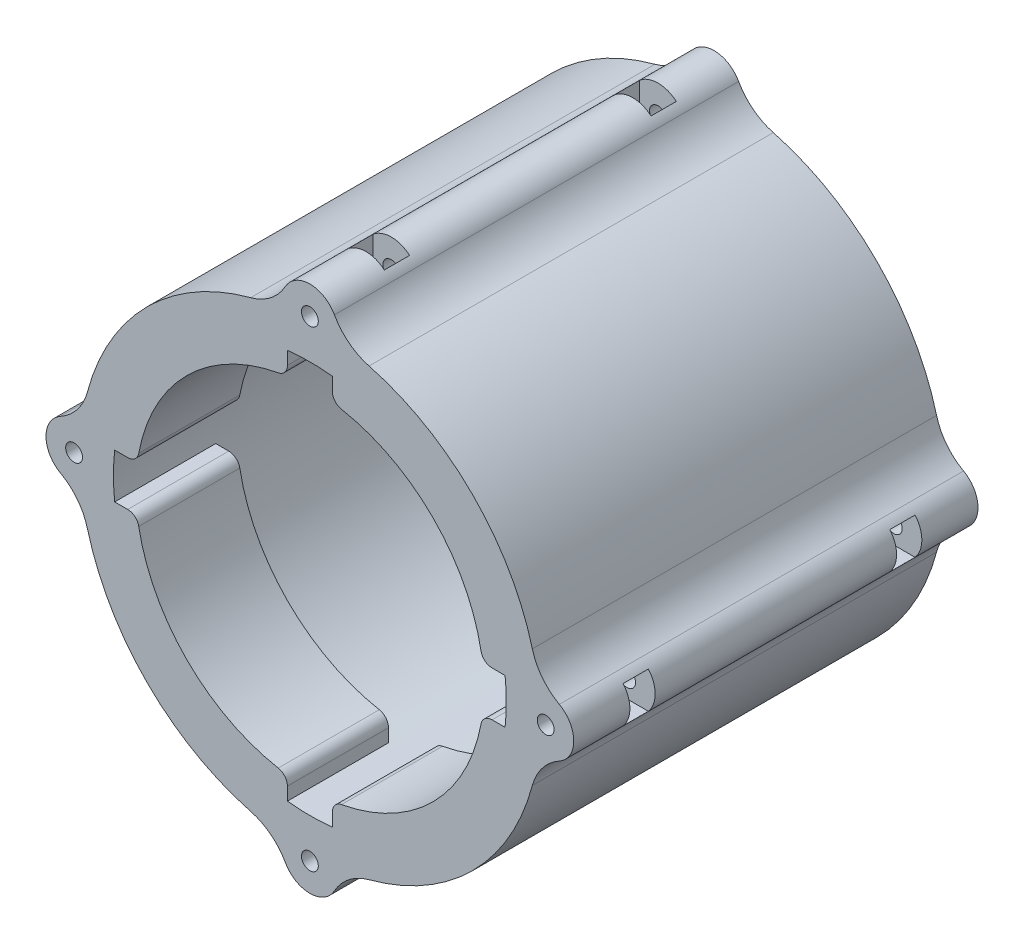
SolidWorks part; units mm, degrees
ref_plane "Ön Düzlem" through (0, 0, 0) normal (0, 0, 1) x (1, 0, 0)
ref_plane "Üst Düzlem" through (0, 0, 0) normal (0, 1, 0) x (1, 0, 0)
ref_plane "Sağ Düzlem" through (0, 0, 0) normal (1, 0, 0) x (0, 0, -1)
sketch "Çizim1" plane through (0, 0, 0) normal (0, 0, 1) x (1, 0, 0)
  circle A0 centre (0, 0) radius 35
  arc A1 (-39.6218, -10.5408) -> (-10.5408, -39.6218) centre (0, 0) ccw
  circle A6 centre (-42, 0) radius 1.5
  arc A7 (-44.4286, 4.3706) -> (-44.4286, -4.3706) centre (-42, 0) ccw
  circle A8 centre (0, 0) radius 41 construction
  arc A9 (-39.6218, -10.5408) -> (-44.4286, -4.3706) centre (-49.2857, -13.1118) ccw
  arc A10 (-39.6218, 10.5408) -> (-44.4286, 4.3706) centre (-49.2857, 13.1118) cw
  circle A11 centre (0, 42) radius 1.5
  arc A12 (4.3706, 44.4286) -> (-4.3706, 44.4286) centre (0, 42) ccw
  arc A13 (-10.5408, 39.6218) -> (-4.3706, 44.4286) centre (-13.1118, 49.2857) ccw
  arc A14 (10.5408, 39.6218) -> (4.3706, 44.4286) centre (13.1118, 49.2857) cw
  circle A15 centre (42, 0) radius 1.5
  arc A16 (44.4286, -4.3706) -> (44.4286, 4.3706) centre (42, 0) ccw
  arc A17 (39.6218, 10.5408) -> (44.4286, 4.3706) centre (49.2857, 13.1118) ccw
  arc A18 (39.6218, -10.5408) -> (44.4286, -4.3706) centre (49.2857, -13.1118) cw
  circle A19 centre (0, -42) radius 1.5
  arc A20 (-4.3706, -44.4286) -> (4.3706, -44.4286) centre (0, -42) ccw
  arc A21 (10.5408, -39.6218) -> (4.3706, -44.4286) centre (13.1118, -49.2857) ccw
  arc A22 (-10.5408, -39.6218) -> (-4.3706, -44.4286) centre (-13.1118, -49.2857) cw
  arc A23 (-10.5408, 39.6218) -> (-39.6218, 10.5408) centre (0, 0) ccw
  arc A24 (39.6218, 10.5408) -> (10.5408, 39.6218) centre (0, 0) ccw
  arc A25 (10.5408, -39.6218) -> (39.6218, -10.5408) centre (0, 0) ccw
  point P13 (0, 0)
  point P14 (-41.4588, 0)
  point P16 (0, 0)
  point P41 (0, 0)
  dimension "D1" = 70
  dimension "D3" = 5
  dimension "D4" = 3
  dimension "D5" = 42
  dimension "D6" = 10
  dimension "D2" = 6
  dimension "D7" = 4
extrude "Yükseklik-Ekstrüzyon1" add sketch "Çizim1" along normal blind 72
sketch "Çizim2" plane through (0, 0, 72) normal (0, 0, 1) x (1, 0, 0)
  line L0 (-4, 34.7707) -> (-4, 32.45)
  line L1 (4, 34.7707) -> (4, 32.45)
  line L2 (34.7707, 4) -> (32.45, 4)
  line L3 (34.7707, -4) -> (32.45, -4)
  line L4 (4, -34.7707) -> (4, -32.45)
  line L5 (-4, -34.7707) -> (-4, -32.45)
  line L6 (-34.7707, -4) -> (-32.45, -4)
  line L7 (-34.7707, 4) -> (-32.45, 4)
  circle A0 centre (0, 0) radius 35 construction
  arc A1 (-4, 34.7707) -> (-34.7707, 4) centre (0, 0) ccw
  arc A2 (-5.6364, 30.4833) -> (-30.4833, 5.6364) centre (0, 0) ccw
  circle A3 centre (0, 0) radius 35 construction
  circle A4 centre (0, 0) radius 31 construction
  arc A5 (4, 32.45) -> (5.6364, 30.4833) centre (6, 32.45) ccw
  arc A6 (-4, 32.45) -> (-5.6364, 30.4833) centre (-6, 32.45) cw
  arc A7 (32.45, 4) -> (30.4833, 5.6364) centre (32.45, 6) cw
  arc A8 (32.45, -4) -> (30.4833, -5.6364) centre (32.45, -6) ccw
  arc A9 (4, -32.45) -> (5.6364, -30.4833) centre (6, -32.45) cw
  arc A10 (-4, -32.45) -> (-5.6364, -30.4833) centre (-6, -32.45) ccw
  arc A11 (-32.45, -4) -> (-30.4833, -5.6364) centre (-32.45, -6) cw
  arc A12 (-32.45, 4) -> (-30.4833, 5.6364) centre (-32.45, 6) ccw
  arc A13 (-30.4833, -5.6364) -> (-5.6364, -30.4833) centre (0, 0) ccw
  arc A14 (-34.7707, -4) -> (-4, -34.7707) centre (0, 0) ccw
  arc A15 (5.6364, -30.4833) -> (30.4833, -5.6364) centre (0, 0) ccw
  arc A16 (4, -34.7707) -> (34.7707, -4) centre (0, 0) ccw
  arc A17 (30.4833, 5.6364) -> (5.6364, 30.4833) centre (0, 0) ccw
  arc A18 (34.7707, 4) -> (4, 34.7707) centre (0, 0) ccw
  point P0 (0, 0)
  point P13 (0, 0)
  point P40 (0, 0)
  dimension "D2" = 4
  dimension "D4" = 2
  dimension "D3" = 4
  dimension "D1" = 4
  dimension "D5" = 4
extrude "Yükseklik-Ekstrüzyon2" add sketch "Çizim2" against normal blind 18
ref_plane "Düzlem1" through (0, 0, 10) normal (0, 0, -1) x (-1, 0, 0)
sketch "Çizim3" plane through (0, 0, 10) normal (0, 0, -1) x (-1, 0, 0)
  line L0 (-3.262, -42) -> (-3.262, -48)
  line L1 (3.262, -42) -> (1.631, -39.175)
  line L2 (1.631, -39.175) -> (-1.631, -39.175)
  line L3 (-1.631, -39.175) -> (-3.262, -42)
  line L7 (3.262, -42) -> (3.262, -48)
  line L8 (3.262, -48) -> (-3.262, -48)
  line L9 (-2.4465, -43.4125) -> (-1.631, -44.825) [skipped]
  line L10 (0, -44.825) -> (1.631, -44.825) [skipped]
  line L11 (2.4465, -43.4125) -> (3.262, -42) [skipped]
  circle A0 centre (0, -42) radius 2.825 construction
  point P1 (0, 0)
  dimension "D1" = 3.262
  dimension "D2" = 6
  dimension "D3" = 6
  dimension "D4" = 3.262
  dimension "D5" = 3.262
extrude "Kes-Ekstrüzyon1" cut sketch "Çizim3" against normal blind 4.5
pattern_circular "Dairesel Kaplama1" count 4 every 90 about axis through (0, 0, 0) along (0, 0, 1) of "Kes-Ekstrüzyon1"
ref_plane "Düzlem2" through (0, 0, 36) normal (0, 0, -1) x (-1, 0, 0)
mirror "Aynalama1" about plane through (0, 0, 36) normal (0, 0, -1) of "Dairesel Kaplama1"
